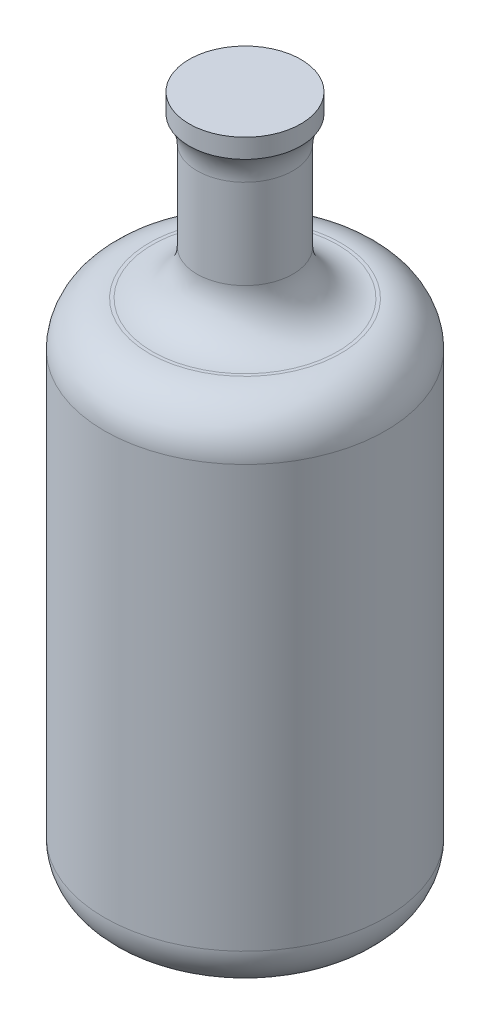
SolidWorks part; units mm, degrees
ref_plane "Plan de face" through (0, 0, 0) normal (0, 0, 1) x (1, 0, 0)
ref_plane "Plan de dessus" through (0, 0, 0) normal (0, 1, 0) x (1, 0, 0)
ref_plane "Plan de droite" through (0, 0, 0) normal (1, 0, 0) x (0, 0, -1)
sketch "Esquisse1" plane through (0, 0, 0) normal (0, 1, 0) x (1, 0, 0)
  circle A0 centre (0, 0) radius 44
  dimension "D1" = 88
extrude "Boss.-Extru.1" add sketch "Esquisse1" along normal blind 160
sketch "Esquisse2" plane through (0, 160, 0) normal (0, 1, 0) x (1, 0, 0)
  circle A0 centre (0, 0) radius 15
  dimension "D1" = 30
extrude "Boss.-Extru.2" add sketch "Esquisse2" along normal blind 50
sketch "Esquisse3" plane through (0, 210, 0) normal (0, 1, 0) x (1, 0, 0)
  circle A0 centre (0, 0) radius 17.5
  dimension "D1" = 35
extrude "Boss.-Extru.3" add sketch "Esquisse3" along normal blind 6
fillet "Congé1" radius 14 2 edges at (0, 160, 15) (0, 160, 44)
fillet "Congé2" radius 14 1 edges at (0, 210, 15)
fillet "Congé3" radius 14 1 edges at (0, 0, 44)
